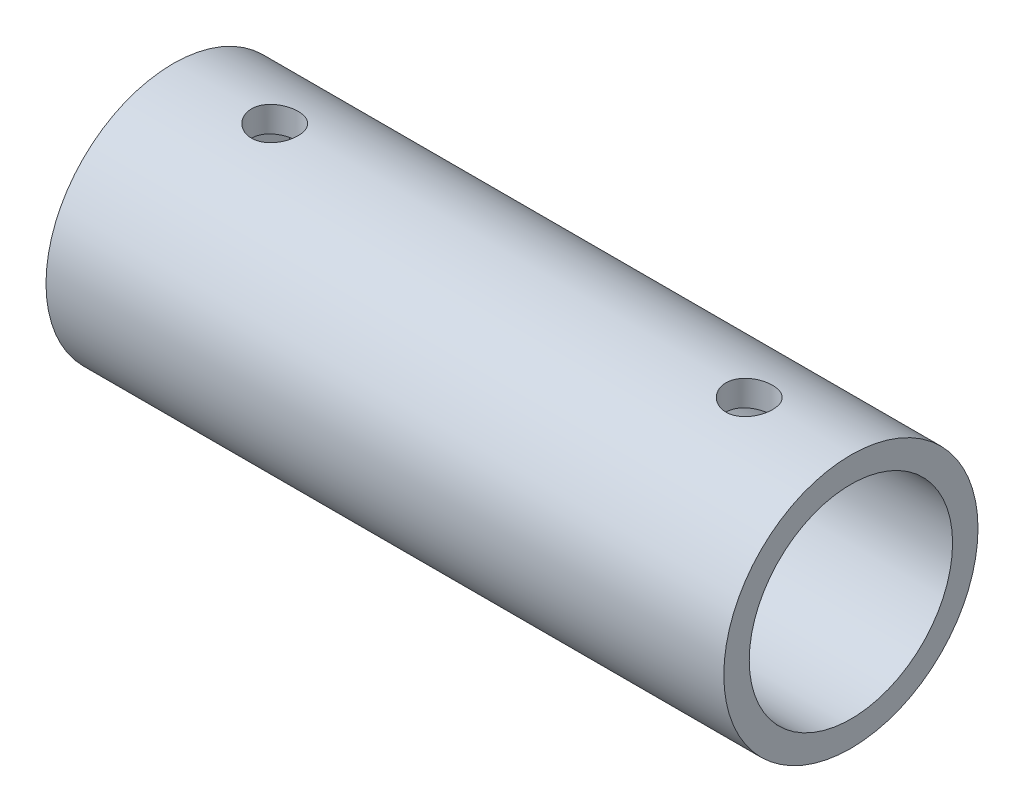
SolidWorks part; units mm, degrees
material "Alloy Steel"
ref_plane "Front Plane" through (0, 0, 0) normal (0, 0, 1) x (1, 0, 0)
ref_plane "Top Plane" through (0, 0, 0) normal (0, 1, 0) x (1, 0, 0)
ref_plane "Right Plane" through (0, 0, 0) normal (1, 0, 0) x (0, 0, -1)
sketch "Sketch1" plane through (0, 0, 0) normal (0, 0, 1) x (1, 0, 0)
  line L0 (-127, 0) -> (127, 0) construction
  line L1 (-127, 0) -> (-127, 47.625)
  line L2 (-127, 47.625) -> (127, 47.625)
  line L3 (127, 47.625) -> (127, 0) construction
  line L4 (-127, 0) -> (-120.65, 0)
  line L5 (-120.65, 0) -> (-120.65, 38.1)
  line L6 (-120.65, 38.1) -> (127, 38.1)
  line L7 (127, 47.625) -> (127, 38.1)
  dimension "D1" = 254
  dimension "D2" = 6.35
  dimension "D3" = 9.525
  dimension "D4" = 38.1
revolve "Revolve1" add sketch "Sketch1" angle 360 about L0
ref_plane "Plane1" through (0, 47.625, 0) normal (0, 1, 0) x (1, 0, 0)
sketch "Sketch2" plane through (0, 47.625, 0) normal (0, 1, 0) x (1, 0, 0)
  line L0 (88.9, 0) -> (-88.9, 0)
  point P4 (0, 0)
  point P6 (-88.9, 0)
  point P7 (88.9, 0)
  dimension "D1" = 177.8
hole_wizard "3/4-16 Tapped Hole1" positions "Sketch4" profile "Sketch3" tap size "3/4-16" standard "ANSI Inch" end condition up to next
sketch "Sketch4" plane through (0, 47.625, 0) normal (0, 1, 0) x (1, 0, 0)
  point P0 (-88.9, 0)
  point P3 (88.9, 0)
sketch "Sketch3" plane through (-88.9, 47.625, 0) normal (1, 0, 0) x (0, 0, 1)
  line L0 (0, 0) -> (0, 9.525)
  line L1 (0, 9.525) -> (8.7312, 9.525)
  line L2 (8.7312, 9.525) -> (8.7312, 0)
  line L5 (8.7312, 0) -> (0, 0)
  line L11 (0, -6.35) -> (0, 107.95) construction
  dimension "Thru Tap Drill Dia." = 17.4625
  dimension "Thru Tap Drill Depth" = 9.525
cosmetic thread "Hole Thread1"
cosmetic thread "Hole Thread2"
ref_plane "Plane2" through (0, 0, 47.625) normal (0, 0, 1) x (1, 0, 0)
sketch "Sketch5" plane through (0, 0, 47.625) normal (0, 0, 1) x (1, 0, 0)
  line L0 (0, 0) -> (-88.9, 0) construction
  point P4 (-88.9, 0)
  dimension "D1" = 88.9
